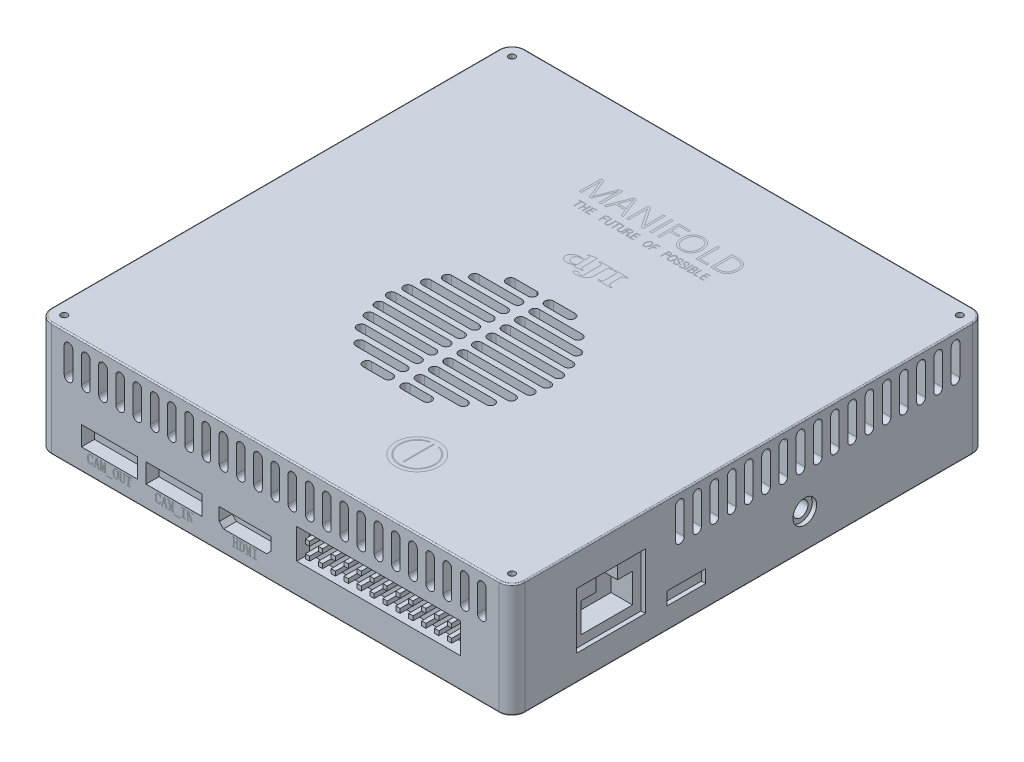
SolidWorks part; units mm, degrees
ref_plane "前视基准面" through (0, 0, 0) normal (0, 0, 1) x (1, 0, 0)
ref_plane "上视基准面" through (0, 0, 0) normal (0, 1, 0) x (1, 0, 0)
ref_plane "右视基准面" through (0, 0, 0) normal (1, 0, 0) x (0, 0, -1)
sketch "草图1" plane through (0, 0, 0) normal (0, 1, 0) x (1, 0, 0)
  line L1 (-55, -55) -> (55, -55)
  line L2 (-55, -55) -> (-55, 55)
  line L3 (-55, 55) -> (55, 55)
  line L4 (55, -55) -> (55, 55)
  line L5 (-55, -55) -> (55, 55) construction
  line L6 (-55, 55) -> (55, -55) construction
  point P0 (0, 0)
  dimension "D1" = 110
extrude "凸台-拉伸1" add sketch "草图1" along normal blind 26.5
fillet "圆角1" radius 3 4 edges at (-55, 13.25, -55) (-55, 13.25, 55) (55, 13.25, -55) (55, 13.25, 55)
sketch "草图2" plane through (0, 26.5, 0) normal (0, 1, 0) x (1, 0, 0)
  line L0 (-55, 33) -> (55, 33) construction
  line L1 (-55, 52) -> (-55, -52) construction
  line L2 (55, -52) -> (55, 52) construction
  line L3 (-55, 29) -> (55, 29) construction
  line L4 (-55, 17) -> (55, 17) construction
  line L5 (52, 55) -> (-52, 55) construction
  line L6 (-52, -55) -> (52, -55) construction
  circle A0 centre (17, -39) radius 5
  text T0 "MANIFOLD" font "@等线" height 5
  text T1 "THE FUTURE OF POSSIBLE" font "汉仪长仿宋体" height 2
  text T2 "dJI" font "@草檀斋毛泽东字体" height 4
  dimension "D4" = 16
  dimension "D5" = 38
  dimension "D6" = 10
  dimension "D1" = 22
  dimension "D2" = 26
  dimension "D3" = 38
split line "分割线1"
sketch "草图3" plane through (0, 26.5, 0) normal (0, 1, 0) x (1, 0, 0)
  line L0 (17, -35) -> (17, -42)
  line L1 (17, -35) -> (17, -34) construction
  line L2 (16.8, -35) -> (16.8, -42)
  arc A0 (15.9647, -35.1363) -> (18.0353, -35.1363) centre (17, -39) ccw
  circle A1 centre (17, -39) radius 5 construction
  arc A2 (15.913, -34.9431) -> (18.087, -34.9431) centre (17, -39) ccw
  arc A3 (18.0353, -35.1363) -> (18.087, -34.9431) centre (18.0612, -35.0397) cw
  arc A4 (15.9647, -35.1363) -> (15.913, -34.9431) centre (15.9388, -35.0397) ccw
  arc A5 (16.8, -35) -> (17, -35) centre (16.9, -35) cw
  arc A6 (16.8, -42) -> (17, -42) centre (16.9, -42) ccw
  dimension "D1" = 4
  dimension "D2" = 4
  dimension "D3" = 7
  dimension "D4" = 30
  dimension "D5" = 0.2
  dimension "D6" = 0.2
split line "分割线3"
sketch "草图4" plane through (0, 26.5, 0) normal (0, 1, 0) x (1, 0, 0)
  line L0 (-52, -55) -> (52, -55) construction
  line L1 (0, 10) -> (0, -30) construction
  line L2 (0, 6.6667) -> (2, 6.6667) construction
  line L3 (0, -26.6667) -> (2, -26.6667) construction
  line L4 (2, -26.6667) -> (2, 6.6667) construction
  line L5 (2, 6.6667) -> (7, 6.6667) construction
  line L6 (2, 7.6667) -> (7, 7.6667)
  line L7 (2, 5.6667) -> (7, 5.6667)
  line L8 (2, 3.3333) -> (12, 3.3333) construction
  line L9 (2, 4.3333) -> (12, 4.3333)
  line L10 (2, 2.3333) -> (12, 2.3333)
  line L11 (2, 0) -> (15, 0) construction
  line L12 (2, 1) -> (15, 1)
  line L13 (2, -1) -> (15, -1)
  line L14 (2, -3.3333) -> (16.5, -3.3333) construction
  line L15 (2, -2.3333) -> (16.5, -2.3333)
  line L16 (2, -4.3333) -> (16.5, -4.3333)
  line L17 (2, -6.6667) -> (17.5, -6.6667) construction
  line L18 (2, -5.6667) -> (17.5, -5.6667)
  line L19 (2, -7.6667) -> (17.5, -7.6667)
  line L20 (2, -10) -> (18, -10) construction
  line L21 (2, -9) -> (18, -9)
  line L22 (2, -11) -> (18, -11)
  line L23 (-20, -10) -> (20, -10) construction
  line L24 (2, -13.3333) -> (17.5, -13.3333) construction
  line L25 (2, -14.3333) -> (17.5, -14.3333)
  line L26 (2, -12.3333) -> (17.5, -12.3333)
  line L27 (2, -16.6667) -> (16.5, -16.6667) construction
  line L28 (2, -17.6667) -> (16.5, -17.6667)
  line L29 (2, -15.6667) -> (16.5, -15.6667)
  line L30 (2, -20) -> (15, -20) construction
  line L31 (2, -21) -> (15, -21)
  line L32 (2, -19) -> (15, -19)
  line L33 (2, -23.3333) -> (12, -23.3333) construction
  line L34 (2, -24.3333) -> (12, -24.3333)
  line L35 (2, -22.3333) -> (12, -22.3333)
  line L36 (2, -26.6667) -> (7, -26.6667) construction
  line L37 (2, -27.6667) -> (7, -27.6667)
  line L38 (2, -25.6667) -> (7, -25.6667)
  line L39 (-2, -26.6667) -> (-7, -26.6667) construction
  line L40 (-2, -27.6667) -> (-7, -27.6667)
  line L41 (-2, -25.6667) -> (-7, -25.6667)
  line L42 (-2, 6.6667) -> (-7, 6.6667) construction
  line L43 (-2, 7.6667) -> (-7, 7.6667)
  line L44 (-2, 5.6667) -> (-7, 5.6667)
  line L45 (-2, 3.3333) -> (-12, 3.3333) construction
  line L46 (-2, 4.3333) -> (-12, 4.3333)
  line L47 (-2, 2.3333) -> (-12, 2.3333)
  line L48 (-2, 0) -> (-15, 0) construction
  line L49 (-2, 1) -> (-15, 1)
  line L50 (-2, -1) -> (-15, -1)
  line L51 (-2, -23.3333) -> (-12, -23.3333) construction
  line L52 (-2, -24.3333) -> (-12, -24.3333)
  line L53 (-2, -22.3333) -> (-12, -22.3333)
  line L54 (-2, -20) -> (-15, -20) construction
  line L55 (-2, -21) -> (-15, -21)
  line L56 (-2, -19) -> (-15, -19)
  line L57 (-2, -16.6667) -> (-16.5, -16.6667) construction
  line L58 (-2, -17.6667) -> (-16.5, -17.6667)
  line L59 (-2, -15.6667) -> (-16.5, -15.6667)
  line L60 (-2, -13.3333) -> (-17.5, -13.3333) construction
  line L61 (-2, -14.3333) -> (-17.5, -14.3333)
  line L62 (-2, -12.3333) -> (-17.5, -12.3333)
  line L63 (-2, -10) -> (-18, -10) construction
  line L64 (-2, -9) -> (-18, -9)
  line L65 (-2, -11) -> (-18, -11)
  line L66 (-2, -6.6667) -> (-17.5, -6.6667) construction
  line L67 (-2, -5.6667) -> (-17.5, -5.6667)
  line L68 (-2, -7.6667) -> (-17.5, -7.6667)
  line L69 (-2, -3.3333) -> (-16.5, -3.3333) construction
  line L70 (-2, -2.3333) -> (-16.5, -2.3333)
  line L71 (-2, -4.3333) -> (-16.5, -4.3333)
  circle A0 centre (0, -10) radius 20 construction
  arc A1 (2, 7.6667) -> (2, 5.6667) centre (2, 6.6667) ccw
  arc A2 (7, 5.6667) -> (7, 7.6667) centre (7, 6.6667) ccw
  arc A3 (2, 4.3333) -> (2, 2.3333) centre (2, 3.3333) ccw
  arc A4 (12, 2.3333) -> (12, 4.3333) centre (12, 3.3333) ccw
  arc A5 (2, 1) -> (2, -1) centre (2, 0) ccw
  arc A6 (15, -1) -> (15, 1) centre (15, 0) ccw
  arc A7 (2, -2.3333) -> (2, -4.3333) centre (2, -3.3333) ccw
  arc A8 (16.5, -4.3333) -> (16.5, -2.3333) centre (16.5, -3.3333) ccw
  arc A9 (2, -5.6667) -> (2, -7.6667) centre (2, -6.6667) ccw
  arc A10 (17.5, -7.6667) -> (17.5, -5.6667) centre (17.5, -6.6667) ccw
  arc A11 (2, -9) -> (2, -11) centre (2, -10) ccw
  arc A12 (18, -11) -> (18, -9) centre (18, -10) ccw
  arc A13 (2, -14.3333) -> (2, -12.3333) centre (2, -13.3333) cw
  arc A14 (17.5, -12.3333) -> (17.5, -14.3333) centre (17.5, -13.3333) cw
  arc A15 (2, -17.6667) -> (2, -15.6667) centre (2, -16.6667) cw
  arc A16 (16.5, -15.6667) -> (16.5, -17.6667) centre (16.5, -16.6667) cw
  arc A17 (2, -21) -> (2, -19) centre (2, -20) cw
  arc A18 (15, -19) -> (15, -21) centre (15, -20) cw
  arc A19 (2, -24.3333) -> (2, -22.3333) centre (2, -23.3333) cw
  arc A20 (12, -22.3333) -> (12, -24.3333) centre (12, -23.3333) cw
  arc A21 (2, -27.6667) -> (2, -25.6667) centre (2, -26.6667) cw
  arc A22 (7, -25.6667) -> (7, -27.6667) centre (7, -26.6667) cw
  arc A23 (-2, -27.6667) -> (-2, -25.6667) centre (-2, -26.6667) ccw
  arc A24 (-7, -25.6667) -> (-7, -27.6667) centre (-7, -26.6667) ccw
  arc A25 (-2, 7.6667) -> (-2, 5.6667) centre (-2, 6.6667) cw
  arc A26 (-7, 5.6667) -> (-7, 7.6667) centre (-7, 6.6667) cw
  arc A27 (-2, 4.3333) -> (-2, 2.3333) centre (-2, 3.3333) cw
  arc A28 (-12, 2.3333) -> (-12, 4.3333) centre (-12, 3.3333) cw
  arc A29 (-2, 1) -> (-2, -1) centre (-2, 0) cw
  arc A30 (-15, -1) -> (-15, 1) centre (-15, 0) cw
  arc A31 (-2, -24.3333) -> (-2, -22.3333) centre (-2, -23.3333) ccw
  arc A32 (-12, -22.3333) -> (-12, -24.3333) centre (-12, -23.3333) ccw
  arc A33 (-2, -21) -> (-2, -19) centre (-2, -20) ccw
  arc A34 (-15, -19) -> (-15, -21) centre (-15, -20) ccw
  arc A35 (-2, -17.6667) -> (-2, -15.6667) centre (-2, -16.6667) ccw
  arc A36 (-16.5, -15.6667) -> (-16.5, -17.6667) centre (-16.5, -16.6667) ccw
  arc A37 (-2, -14.3333) -> (-2, -12.3333) centre (-2, -13.3333) ccw
  arc A38 (-17.5, -12.3333) -> (-17.5, -14.3333) centre (-17.5, -13.3333) ccw
  arc A39 (-2, -9) -> (-2, -11) centre (-2, -10) cw
  arc A40 (-18, -11) -> (-18, -9) centre (-18, -10) cw
  arc A41 (-2, -5.6667) -> (-2, -7.6667) centre (-2, -6.6667) cw
  arc A42 (-17.5, -7.6667) -> (-17.5, -5.6667) centre (-17.5, -6.6667) cw
  arc A43 (-2, -2.3333) -> (-2, -4.3333) centre (-2, -3.3333) cw
  arc A44 (-16.5, -4.3333) -> (-16.5, -2.3333) centre (-16.5, -3.3333) cw
  point P5 (0, -55)
  point P11 (2, -23.3333)
  point P12 (2, -20)
  point P13 (2, -16.6667)
  point P14 (2, -13.3333)
  point P15 (2, -10)
  point P16 (2, -6.6667)
  point P17 (2, -3.3333)
  point P18 (2, 0)
  point P19 (2, 3.3333)
  point P20 (4.5, 6.6667)
  point P26 (7, 3.3333)
  point P33 (8.5, 0)
  point P42 (9.25, -3.3333)
  point P47 (9.75, -6.6667)
  point P49 (0, 6.6667)
  point P50 (0, 3.3333)
  point P51 (0, 0)
  point P52 (0, -3.3333)
  point P53 (0, -6.6667)
  point P54 (0, -10)
  point P55 (0, -13.3333)
  point P56 (0, -16.6667)
  point P57 (0, -20)
  point P58 (0, -23.3333)
  point P59 (0, -26.6667)
  point P66 (10, -10)
  point P76 (9.75, -13.3333)
  point P83 (9.25, -16.6667)
  point P90 (8.5, -20)
  point P97 (7, -23.3333)
  point P103 (4.5, -26.6667)
  point P110 (-4.5, -26.6667)
  point P117 (-4.5, 6.6667)
  point P124 (-7, 3.3333)
  point P131 (-8.5, 0)
  point P139 (-7, -23.3333)
  point P146 (-8.5, -20)
  point P153 (-9.25, -16.6667)
  point P160 (-9.75, -13.3333)
  point P167 (-10, -10)
  point P174 (-9.75, -6.6667)
  point P181 (-9.25, -3.3333)
  dimension "D1" = 40
  dimension "D3" = 1
  dimension "D4" = 1
  dimension "D5" = 1
  dimension "D6" = 1
  dimension "D7" = 1
  dimension "D8" = 1
  dimension "D9" = 2
  dimension "D2" = 45
  dimension "D10" = 5
  dimension "D11" = 10
  dimension "D12" = 13
  dimension "D13" = 14.5
  dimension "D14" = 15.5
  dimension "D15" = 16
extrude "切除-拉伸1" cut sketch "草图4" against normal blind 6
sketch "草图5" plane through (0, 0, 55) normal (0, 0, 1) x (1, 0, 0)
  line L0 (55, 26.5) -> (55, 0) construction
  line L1 (5, 14) -> (43, 14)
  line L2 (5, 14) -> (5, 7)
  line L3 (5, 7) -> (43, 7)
  line L4 (43, 14) -> (43, 7)
  line L5 (-52, 0) -> (52, 0) construction
  line L6 (-13, 9) -> (-1, 9)
  line L7 (-1, 9) -> (-1, 6)
  line L8 (-1, 6) -> (-2, 5)
  line L9 (-2, 5) -> (-12, 5)
  line L10 (-12, 5) -> (-13, 6)
  line L11 (-13, 6) -> (-13, 9)
  line L12 (-55, 0) -> (-55, 26.5) construction
  line L13 (-45, 9.5) -> (-32, 9.5)
  line L14 (-45, 9.5) -> (-45, 5)
  line L15 (-45, 5) -> (-32, 5)
  line L16 (-32, 9.5) -> (-32, 5)
  line L17 (-30, 9.5) -> (-17, 9.5)
  line L18 (-30, 9.5) -> (-30, 5)
  line L19 (-30, 5) -> (-17, 5)
  line L20 (-17, 9.5) -> (-17, 5)
  line L21 (10, 12.5) -> (11, 12.5)
  line L22 (7, 12.5) -> (8, 12.5)
  line L23 (7, 12.5) -> (7, 11.5)
  line L24 (7, 11.5) -> (8, 11.5)
  line L25 (8, 12.5) -> (8, 11.5)
  line L26 (11, 12.5) -> (11, 11.5)
  line L27 (10, 11.5) -> (11, 11.5)
  line L28 (10, 12.5) -> (10, 11.5)
  line L29 (13, 12.5) -> (14, 12.5)
  line L30 (14, 12.5) -> (14, 11.5)
  line L31 (13, 11.5) -> (14, 11.5)
  line L32 (13, 12.5) -> (13, 11.5)
  line L33 (16, 12.5) -> (17, 12.5)
  line L34 (17, 12.5) -> (17, 11.5)
  line L35 (16, 11.5) -> (17, 11.5)
  line L36 (16, 12.5) -> (16, 11.5)
  line L37 (19, 12.5) -> (20, 12.5)
  line L38 (20, 12.5) -> (20, 11.5)
  line L39 (19, 11.5) -> (20, 11.5)
  line L40 (19, 12.5) -> (19, 11.5)
  line L41 (22, 12.5) -> (23, 12.5)
  line L42 (23, 12.5) -> (23, 11.5)
  line L43 (22, 11.5) -> (23, 11.5)
  line L44 (22, 12.5) -> (22, 11.5)
  line L45 (25, 12.5) -> (26, 12.5)
  line L46 (26, 12.5) -> (26, 11.5)
  line L47 (25, 11.5) -> (26, 11.5)
  line L48 (25, 12.5) -> (25, 11.5)
  line L49 (28, 12.5) -> (29, 12.5)
  line L50 (29, 12.5) -> (29, 11.5)
  line L51 (28, 11.5) -> (29, 11.5)
  line L52 (28, 12.5) -> (28, 11.5)
  line L53 (31, 12.5) -> (32, 12.5)
  line L54 (32, 12.5) -> (32, 11.5)
  line L55 (31, 11.5) -> (32, 11.5)
  line L56 (31, 12.5) -> (31, 11.5)
  line L57 (34, 12.5) -> (35, 12.5)
  line L58 (35, 12.5) -> (35, 11.5)
  line L59 (34, 11.5) -> (35, 11.5)
  line L60 (34, 12.5) -> (34, 11.5)
  line L61 (37, 12.5) -> (38, 12.5)
  line L62 (38, 12.5) -> (38, 11.5)
  line L63 (37, 11.5) -> (38, 11.5)
  line L64 (37, 12.5) -> (37, 11.5)
  line L65 (40, 12.5) -> (41, 12.5)
  line L66 (41, 12.5) -> (41, 11.5)
  line L67 (40, 11.5) -> (41, 11.5)
  line L68 (40, 12.5) -> (40, 11.5)
  line L69 (10, 9.5) -> (11, 9.5)
  line L70 (11, 9.5) -> (11, 8.5)
  line L71 (10, 8.5) -> (11, 8.5)
  line L72 (10, 9.5) -> (10, 8.5)
  line L73 (13, 9.5) -> (14, 9.5)
  line L74 (14, 9.5) -> (14, 8.5)
  line L75 (13, 8.5) -> (14, 8.5)
  line L76 (13, 9.5) -> (13, 8.5)
  line L77 (16, 9.5) -> (17, 9.5)
  line L78 (17, 9.5) -> (17, 8.5)
  line L79 (16, 8.5) -> (17, 8.5)
  line L80 (16, 9.5) -> (16, 8.5)
  line L81 (19, 9.5) -> (20, 9.5)
  line L82 (20, 9.5) -> (20, 8.5)
  line L83 (19, 8.5) -> (20, 8.5)
  line L84 (19, 9.5) -> (19, 8.5)
  line L85 (22, 9.5) -> (23, 9.5)
  line L86 (23, 9.5) -> (23, 8.5)
  line L87 (22, 8.5) -> (23, 8.5)
  line L88 (22, 9.5) -> (22, 8.5)
  line L89 (25, 9.5) -> (26, 9.5)
  line L90 (26, 9.5) -> (26, 8.5)
  line L91 (25, 8.5) -> (26, 8.5)
  line L92 (25, 9.5) -> (25, 8.5)
  line L93 (28, 9.5) -> (29, 9.5)
  line L94 (29, 9.5) -> (29, 8.5)
  line L95 (28, 8.5) -> (29, 8.5)
  line L96 (28, 9.5) -> (28, 8.5)
  line L97 (31, 9.5) -> (32, 9.5)
  line L98 (32, 9.5) -> (32, 8.5)
  line L99 (31, 8.5) -> (32, 8.5)
  line L100 (31, 9.5) -> (31, 8.5)
  line L101 (34, 9.5) -> (35, 9.5)
  line L102 (35, 9.5) -> (35, 8.5)
  line L103 (34, 8.5) -> (35, 8.5)
  line L104 (34, 9.5) -> (34, 8.5)
  line L105 (37, 9.5) -> (38, 9.5)
  line L106 (38, 9.5) -> (38, 8.5)
  line L107 (37, 8.5) -> (38, 8.5)
  line L108 (37, 9.5) -> (37, 8.5)
  line L109 (40, 9.5) -> (41, 9.5)
  line L110 (41, 9.5) -> (41, 8.5)
  line L111 (40, 8.5) -> (41, 8.5)
  line L112 (40, 9.5) -> (40, 8.5)
  line L113 (7, 9.5) -> (8, 9.5)
  line L114 (8, 9.5) -> (8, 8.5)
  line L115 (7, 8.5) -> (8, 8.5)
  line L116 (7, 9.5) -> (7, 8.5)
  line L117 (7, 12.5) -> (10, 12.5) construction
  line L118 (7, 12.5) -> (7, 9.5) construction
  point P16 (-7, 5)
  point P17 (-7, 9)
  point P25 (-30, 7.25)
  dimension "D1" = 12
  dimension "D2" = 7
  dimension "D3" = 38
  dimension "D4" = 7
  dimension "D5" = 12
  dimension "D6" = 4
  dimension "D7" = 3
  dimension "D8" = 10
  dimension "D9" = 5
  dimension "D10" = 6
  dimension "D11" = 4.5
  dimension "D12" = 5
  dimension "D13" = 13
  dimension "D14" = 2
  dimension "D15" = 10
  dimension "D16" = 1
  dimension "D17" = 1.5
  dimension "D18" = 2
  dimension "D21" = 3
  dimension "D22" = 3
  dimension "D19" = 12
  dimension "D20" = 2
extrude "切除-拉伸2" cut sketch "草图5" against normal blind 3
sketch "草图6" plane through (55, 0, 0) normal (1, 0, 0) x (0, 0, -1)
  line L0 (-52, 0) -> (52, 0) construction
  line L1 (-40, 6) -> (-24, 6)
  line L2 (-40, 6) -> (-40, 19)
  line L3 (-40, 19) -> (-24, 19)
  line L4 (-24, 6) -> (-24, 19)
  line L5 (-55, 0) -> (-55, 26.5) construction
  line L6 (55, 26.5) -> (55, 0) construction
  line L7 (-19, 8) -> (-10, 8)
  line L8 (-19, 8) -> (-19, 5)
  line L9 (-19, 5) -> (-10, 5)
  line L10 (-10, 8) -> (-10, 5)
  circle A0 centre (13, 8) radius 2.75
  dimension "D9" = 5.5
  dimension "D10" = 8
  dimension "D11" = 42
  dimension "D1" = 6
  dimension "D2" = 16
  dimension "D3" = 13
  dimension "D4" = 15
  dimension "D5" = 5
  dimension "D6" = 3
  dimension "D7" = 9
  dimension "D8" = 5
extrude "切除-拉伸3" cut sketch "草图6" against normal blind 1
sketch "草图7" plane through (54, 0, 0) normal (1, 0, 0) x (0, 0, -1)
  line L0 (-29.5, 15) -> (-26, 15)
  line L1 (-38, 8.2) -> (-26, 8.2)
  line L2 (-38, 8.2) -> (-38, 15)
  line L3 (-38, 15) -> (-34.5, 15)
  line L4 (-26, 8.2) -> (-26, 15)
  line L5 (-34.5, 18.5) -> (-29.5, 18.5)
  line L6 (-34.5, 18.5) -> (-34.5, 15)
  line L7 (-40, 6) -> (-24, 6) construction
  line L8 (-29.5, 18.5) -> (-29.5, 15)
  line L9 (-24, 6) -> (-24, 19) construction
  line L10 (-40, 6) -> (-24, 6) construction
  line L11 (-24, 19) -> (-40, 19) construction
  point P13 (-32, 8.2)
  point P16 (-32, 6)
  dimension "D1" = 2.2
  dimension "D2" = 2
  dimension "D3" = 5
  dimension "D4" = 4
  dimension "D5" = 0.5
extrude "切除-拉伸4" cut sketch "草图7" against normal blind 5
sketch "草图8" plane through (-55, 0, 0) normal (-1, 0, 0) x (0, 0, 1)
  line L0 (-52, 0) -> (52, 0) construction
  line L1 (38, 19) -> (44, 19)
  line L2 (38, 19) -> (38, 6)
  line L3 (38, 6) -> (44, 6)
  line L4 (44, 19) -> (44, 6)
  line L5 (28.5, 19) -> (34.5, 19)
  line L6 (28.5, 19) -> (28.5, 6)
  line L7 (28.5, 6) -> (34.5, 6)
  line L8 (34.5, 19) -> (34.5, 6)
  line L9 (10, 21) -> (25, 21)
  line L10 (10, 21) -> (10, 6)
  line L11 (10, 6) -> (25, 6)
  line L12 (25, 21) -> (25, 6)
  line L13 (-13.5, 9.5) -> (-5.5, 9.5)
  line L14 (-13.5, 9.5) -> (-13.5, 5)
  line L15 (-13.5, 5) -> (-5.5, 5)
  line L16 (-5.5, 9.5) -> (-5.5, 5)
  line L17 (-4, 9.5) -> (6.5, 9.5)
  line L18 (-4, 9.5) -> (-4, 5)
  line L19 (-4, 5) -> (6.5, 5)
  line L20 (6.5, 9.5) -> (6.5, 5)
  line L21 (-44, 17) -> (-31, 17)
  line L22 (-44, 17) -> (-44, 6)
  line L23 (-44, 6) -> (-31, 6)
  line L24 (-31, 17) -> (-31, 6)
  line L25 (55, 26.5) -> (55, 0) construction
  line L26 (-55, 0) -> (-55, 26.5) construction
  point P24 (31.5, 19)
  point P30 (28.5, 12.5)
  dimension "D1" = 6
  dimension "D2" = 13
  dimension "D3" = 6
  dimension "D4" = 11
  dimension "D5" = 3.5
  dimension "D6" = 3.5
  dimension "D7" = 6
  dimension "D8" = 15
  dimension "D9" = 5
  dimension "D10" = 4.5
  dimension "D11" = 10.5
  dimension "D12" = 8
  dimension "D13" = 1.5
  dimension "D14" = 3.5
  dimension "D15" = 11
  dimension "D16" = 11
  dimension "D17" = 13
  dimension "D18" = 6
extrude "切除-拉伸5" cut sketch "草图8" against normal blind 1
sketch "草图9" plane through (55, 0, 0) normal (1, 0, 0) x (0, 0, -1)
  line L0 (-52, 26.5) -> (52, 26.5) construction
  line L1 (48, 24) -> (48, 17) construction
  line L2 (49, 24) -> (49, 17)
  line L3 (-16, 14.5) -> (52, 14.5) construction
  line L4 (47, 24) -> (47, 17)
  line L5 (52, 0) -> (52, 26.5) construction
  line L6 (44, 24) -> (44, 17) construction
  line L7 (45, 24) -> (45, 17)
  line L8 (43, 24) -> (43, 17)
  line L9 (40, 24) -> (40, 17) construction
  line L10 (41, 24) -> (41, 17)
  line L11 (39, 24) -> (39, 17)
  line L12 (36, 24) -> (36, 17) construction
  line L13 (37, 24) -> (37, 17)
  line L14 (35, 24) -> (35, 17)
  line L15 (32, 24) -> (32, 17) construction
  line L16 (33, 24) -> (33, 17)
  line L17 (31, 24) -> (31, 17)
  line L18 (28, 24) -> (28, 17) construction
  line L19 (29, 24) -> (29, 17)
  line L20 (27, 24) -> (27, 17)
  line L21 (24, 24) -> (24, 17) construction
  line L22 (25, 24) -> (25, 17)
  line L23 (23, 24) -> (23, 17)
  line L24 (20, 24) -> (20, 17) construction
  line L25 (21, 24) -> (21, 17)
  line L26 (19, 24) -> (19, 17)
  line L27 (16, 24) -> (16, 17) construction
  line L28 (17, 24) -> (17, 17)
  line L29 (15, 24) -> (15, 17)
  line L30 (12, 24) -> (12, 17) construction
  line L31 (13, 24) -> (13, 17)
  line L32 (11, 24) -> (11, 17)
  line L33 (8, 24) -> (8, 17) construction
  line L34 (9, 24) -> (9, 17)
  line L35 (7, 24) -> (7, 17)
  line L36 (4, 24) -> (4, 17) construction
  line L37 (5, 24) -> (5, 17)
  line L38 (3, 24) -> (3, 17)
  line L39 (0, 24) -> (0, 17) construction
  line L40 (1, 24) -> (1, 17)
  line L41 (-1, 24) -> (-1, 17)
  line L42 (-4, 24) -> (-4, 17) construction
  line L43 (-3, 24) -> (-3, 17)
  line L44 (-5, 24) -> (-5, 17)
  line L45 (-8, 24) -> (-8, 17) construction
  line L46 (-7, 24) -> (-7, 17)
  line L47 (-9, 24) -> (-9, 17)
  line L48 (-12, 24) -> (-12, 17) construction
  line L49 (-11, 24) -> (-11, 17)
  line L50 (-13, 24) -> (-13, 17)
  line L51 (-16, 24) -> (-16, 17) construction
  line L52 (-15, 24) -> (-15, 17)
  line L53 (-17, 24) -> (-17, 17)
  arc A0 (49, 24) -> (47, 24) centre (48, 24) ccw
  arc A1 (47, 17) -> (49, 17) centre (48, 17) ccw
  arc A2 (45, 24) -> (43, 24) centre (44, 24) ccw
  arc A3 (43, 17) -> (45, 17) centre (44, 17) ccw
  arc A4 (41, 24) -> (39, 24) centre (40, 24) ccw
  arc A5 (39, 17) -> (41, 17) centre (40, 17) ccw
  arc A6 (37, 24) -> (35, 24) centre (36, 24) ccw
  arc A7 (35, 17) -> (37, 17) centre (36, 17) ccw
  arc A8 (33, 24) -> (31, 24) centre (32, 24) ccw
  arc A9 (31, 17) -> (33, 17) centre (32, 17) ccw
  arc A10 (29, 24) -> (27, 24) centre (28, 24) ccw
  arc A11 (27, 17) -> (29, 17) centre (28, 17) ccw
  arc A12 (25, 24) -> (23, 24) centre (24, 24) ccw
  arc A13 (23, 17) -> (25, 17) centre (24, 17) ccw
  arc A14 (21, 24) -> (19, 24) centre (20, 24) ccw
  arc A15 (19, 17) -> (21, 17) centre (20, 17) ccw
  arc A16 (17, 24) -> (15, 24) centre (16, 24) ccw
  arc A17 (15, 17) -> (17, 17) centre (16, 17) ccw
  arc A18 (13, 24) -> (11, 24) centre (12, 24) ccw
  arc A19 (11, 17) -> (13, 17) centre (12, 17) ccw
  arc A20 (9, 24) -> (7, 24) centre (8, 24) ccw
  arc A21 (7, 17) -> (9, 17) centre (8, 17) ccw
  arc A22 (5, 24) -> (3, 24) centre (4, 24) ccw
  arc A23 (3, 17) -> (5, 17) centre (4, 17) ccw
  arc A24 (1, 24) -> (-1, 24) centre (0, 24) ccw
  arc A25 (-1, 17) -> (1, 17) centre (0, 17) ccw
  arc A26 (-3, 24) -> (-5, 24) centre (-4, 24) ccw
  arc A27 (-5, 17) -> (-3, 17) centre (-4, 17) ccw
  arc A28 (-7, 24) -> (-9, 24) centre (-8, 24) ccw
  arc A29 (-9, 17) -> (-7, 17) centre (-8, 17) ccw
  arc A30 (-11, 24) -> (-13, 24) centre (-12, 24) ccw
  arc A31 (-13, 17) -> (-11, 17) centre (-12, 17) ccw
  arc A32 (-15, 24) -> (-17, 24) centre (-16, 24) ccw
  arc A33 (-17, 17) -> (-15, 17) centre (-16, 17) ccw
  point P6 (48, 20.5)
  point P16 (44, 20.5)
  point P23 (40, 20.5)
  point P30 (36, 20.5)
  point P37 (32, 20.5)
  point P44 (28, 20.5)
  point P51 (24, 20.5)
  point P58 (20, 20.5)
  point P65 (16, 20.5)
  point P72 (12, 20.5)
  point P79 (8, 20.5)
  point P86 (4, 20.5)
  point P93 (0, 20.5)
  point P100 (-4, 20.5)
  point P107 (-8, 20.5)
  point P114 (-12, 20.5)
  point P121 (-16, 20.5)
  dimension "D2" = 1
  dimension "D1" = 12
  dimension "D3" = 4
  dimension "D4" = 7
  dimension "D5" = 2.5
  dimension "D7" = 4
  dimension "D6" = 17
extrude "切除-拉伸6" cut sketch "草图9" against normal blind 5
sketch "草图10" plane through (0, 0, -55) normal (0, 0, -1) x (-1, 0, 0)
  line L0 (-48, 24) -> (-48, 17) construction
  line L1 (-47, 24) -> (-47, 17)
  line L2 (-49, 24) -> (-49, 17)
  line L3 (-52, 26.5) -> (52, 26.5) construction
  line L4 (-52, 26.5) -> (-52, 0) construction
  line L5 (-44, 24) -> (-44, 17) construction
  line L6 (-43, 24) -> (-43, 17)
  line L7 (-45, 24) -> (-45, 17)
  line L8 (-40, 24) -> (-40, 17) construction
  line L9 (-39, 24) -> (-39, 17)
  line L10 (-41, 24) -> (-41, 17)
  line L11 (-36, 24) -> (-36, 17) construction
  line L12 (-35, 24) -> (-35, 17)
  line L13 (-37, 24) -> (-37, 17)
  line L14 (-32, 24) -> (-32, 17) construction
  line L15 (-31, 24) -> (-31, 17)
  line L16 (-33, 24) -> (-33, 17)
  line L17 (-28, 24) -> (-28, 17) construction
  line L18 (-27, 24) -> (-27, 17)
  line L19 (-29, 24) -> (-29, 17)
  line L20 (-24, 24) -> (-24, 17) construction
  line L21 (-23, 24) -> (-23, 17)
  line L22 (-25, 24) -> (-25, 17)
  line L23 (-20, 24) -> (-20, 17) construction
  line L24 (-19, 24) -> (-19, 17)
  line L25 (-21, 24) -> (-21, 17)
  line L26 (-16, 24) -> (-16, 17) construction
  line L27 (-15, 24) -> (-15, 17)
  line L28 (-17, 24) -> (-17, 17)
  line L29 (-12, 24) -> (-12, 17) construction
  line L30 (-11, 24) -> (-11, 17)
  line L31 (-13, 24) -> (-13, 17)
  line L32 (-8, 24) -> (-8, 17) construction
  line L33 (-7, 24) -> (-7, 17)
  line L34 (-9, 24) -> (-9, 17)
  line L35 (-4, 24) -> (-4, 17) construction
  line L36 (-3, 24) -> (-3, 17)
  line L37 (-5, 24) -> (-5, 17)
  line L38 (0, 24) -> (0, 17) construction
  line L39 (1, 24) -> (1, 17)
  line L40 (-1, 24) -> (-1, 17)
  line L41 (4, 24) -> (4, 17) construction
  line L42 (5, 24) -> (5, 17)
  line L43 (3, 24) -> (3, 17)
  line L44 (8, 24) -> (8, 17) construction
  line L45 (9, 24) -> (9, 17)
  line L46 (7, 24) -> (7, 17)
  line L47 (12, 24) -> (12, 17) construction
  line L48 (13, 24) -> (13, 17)
  line L49 (11, 24) -> (11, 17)
  line L50 (16, 24) -> (16, 17) construction
  line L51 (17, 24) -> (17, 17)
  line L52 (15, 24) -> (15, 17)
  line L53 (20, 24) -> (20, 17) construction
  line L54 (21, 24) -> (21, 17)
  line L55 (19, 24) -> (19, 17)
  line L56 (24, 24) -> (24, 17) construction
  line L57 (25, 24) -> (25, 17)
  line L58 (23, 24) -> (23, 17)
  line L59 (28, 24) -> (28, 17) construction
  line L60 (29, 24) -> (29, 17)
  line L61 (27, 24) -> (27, 17)
  line L62 (32, 24) -> (32, 17) construction
  line L63 (33, 24) -> (33, 17)
  line L64 (31, 24) -> (31, 17)
  line L65 (36, 24) -> (36, 17) construction
  line L66 (37, 24) -> (37, 17)
  line L67 (35, 24) -> (35, 17)
  line L68 (40, 24) -> (40, 17) construction
  line L69 (41, 24) -> (41, 17)
  line L70 (39, 24) -> (39, 17)
  line L71 (44, 24) -> (44, 17) construction
  line L72 (45, 24) -> (45, 17)
  line L73 (43, 24) -> (43, 17)
  line L74 (48, 24) -> (48, 17) construction
  line L75 (49, 24) -> (49, 17)
  line L76 (47, 24) -> (47, 17)
  line L77 (-48, 24) -> (-44, 24) construction
  arc A0 (-47, 24) -> (-49, 24) centre (-48, 24) ccw
  arc A1 (-49, 17) -> (-47, 17) centre (-48, 17) ccw
  arc A2 (-43, 24) -> (-45, 24) centre (-44, 24) ccw
  arc A3 (-45, 17) -> (-43, 17) centre (-44, 17) ccw
  arc A4 (-39, 24) -> (-41, 24) centre (-40, 24) ccw
  arc A5 (-41, 17) -> (-39, 17) centre (-40, 17) ccw
  arc A6 (-35, 24) -> (-37, 24) centre (-36, 24) ccw
  arc A7 (-37, 17) -> (-35, 17) centre (-36, 17) ccw
  arc A8 (-31, 24) -> (-33, 24) centre (-32, 24) ccw
  arc A9 (-33, 17) -> (-31, 17) centre (-32, 17) ccw
  arc A10 (-27, 24) -> (-29, 24) centre (-28, 24) ccw
  arc A11 (-29, 17) -> (-27, 17) centre (-28, 17) ccw
  arc A12 (-23, 24) -> (-25, 24) centre (-24, 24) ccw
  arc A13 (-25, 17) -> (-23, 17) centre (-24, 17) ccw
  arc A14 (-19, 24) -> (-21, 24) centre (-20, 24) ccw
  arc A15 (-21, 17) -> (-19, 17) centre (-20, 17) ccw
  arc A16 (-15, 24) -> (-17, 24) centre (-16, 24) ccw
  arc A17 (-17, 17) -> (-15, 17) centre (-16, 17) ccw
  arc A18 (-11, 24) -> (-13, 24) centre (-12, 24) ccw
  arc A19 (-13, 17) -> (-11, 17) centre (-12, 17) ccw
  arc A20 (-7, 24) -> (-9, 24) centre (-8, 24) ccw
  arc A21 (-9, 17) -> (-7, 17) centre (-8, 17) ccw
  arc A22 (-3, 24) -> (-5, 24) centre (-4, 24) ccw
  arc A23 (-5, 17) -> (-3, 17) centre (-4, 17) ccw
  arc A24 (1, 24) -> (-1, 24) centre (0, 24) ccw
  arc A25 (-1, 17) -> (1, 17) centre (0, 17) ccw
  arc A26 (5, 24) -> (3, 24) centre (4, 24) ccw
  arc A27 (3, 17) -> (5, 17) centre (4, 17) ccw
  arc A28 (9, 24) -> (7, 24) centre (8, 24) ccw
  arc A29 (7, 17) -> (9, 17) centre (8, 17) ccw
  arc A30 (13, 24) -> (11, 24) centre (12, 24) ccw
  arc A31 (11, 17) -> (13, 17) centre (12, 17) ccw
  arc A32 (17, 24) -> (15, 24) centre (16, 24) ccw
  arc A33 (15, 17) -> (17, 17) centre (16, 17) ccw
  arc A34 (21, 24) -> (19, 24) centre (20, 24) ccw
  arc A35 (19, 17) -> (21, 17) centre (20, 17) ccw
  arc A36 (25, 24) -> (23, 24) centre (24, 24) ccw
  arc A37 (23, 17) -> (25, 17) centre (24, 17) ccw
  arc A38 (29, 24) -> (27, 24) centre (28, 24) ccw
  arc A39 (27, 17) -> (29, 17) centre (28, 17) ccw
  arc A40 (33, 24) -> (31, 24) centre (32, 24) ccw
  arc A41 (31, 17) -> (33, 17) centre (32, 17) ccw
  arc A42 (37, 24) -> (35, 24) centre (36, 24) ccw
  arc A43 (35, 17) -> (37, 17) centre (36, 17) ccw
  arc A44 (41, 24) -> (39, 24) centre (40, 24) ccw
  arc A45 (39, 17) -> (41, 17) centre (40, 17) ccw
  arc A46 (45, 24) -> (43, 24) centre (44, 24) ccw
  arc A47 (43, 17) -> (45, 17) centre (44, 17) ccw
  arc A48 (49, 24) -> (47, 24) centre (48, 24) ccw
  arc A49 (47, 17) -> (49, 17) centre (48, 17) ccw
  point P2 (-48, 20.5)
  point P14 (-44, 20.5)
  point P21 (-40, 20.5)
  point P28 (-36, 20.5)
  point P35 (-32, 20.5)
  point P42 (-28, 20.5)
  point P49 (-24, 20.5)
  point P56 (-20, 20.5)
  point P63 (-16, 20.5)
  point P70 (-12, 20.5)
  point P77 (-8, 20.5)
  point P84 (-4, 20.5)
  point P91 (0, 20.5)
  point P98 (4, 20.5)
  point P105 (8, 20.5)
  point P112 (12, 20.5)
  point P119 (16, 20.5)
  point P126 (20, 20.5)
  point P133 (24, 20.5)
  point P140 (28, 20.5)
  point P147 (32, 20.5)
  point P154 (36, 20.5)
  point P161 (40, 20.5)
  point P168 (44, 20.5)
  point P175 (48, 20.5)
  dimension "D1" = 2.5
  dimension "D2" = 1
  dimension "D3" = 7
  dimension "D4" = 4
  dimension "D6" = 4
  dimension "D5" = 25
extrude "切除-拉伸7" cut sketch "草图10" against normal blind 5
sketch "草图11" plane through (0, 0, 55) normal (0, 0, 1) x (1, 0, 0)
  line L0 (-52, 26.5) -> (52, 26.5) construction
  line L1 (-52, 26.5) -> (-52, 0) construction
  line L2 (52, 0) -> (52, 26.5) construction
  line L3 (-52, 14.5) -> (52, 14.5) construction
  line L4 (-48, 17.5) -> (-48, 23.5) construction
  line L5 (-49, 17.5) -> (-49, 23.5)
  line L6 (-47, 17.5) -> (-47, 23.5)
  line L7 (-44, 17.5) -> (-44, 23.5) construction
  line L8 (-45, 17.5) -> (-45, 23.5)
  line L9 (-43, 17.5) -> (-43, 23.5)
  line L10 (-40, 17.5) -> (-40, 23.5) construction
  line L11 (-41, 17.5) -> (-41, 23.5)
  line L12 (-39, 17.5) -> (-39, 23.5)
  line L13 (-36, 17.5) -> (-36, 23.5) construction
  line L14 (-37, 17.5) -> (-37, 23.5)
  line L15 (-35, 17.5) -> (-35, 23.5)
  line L16 (-32, 17.5) -> (-32, 23.5) construction
  line L17 (-33, 17.5) -> (-33, 23.5)
  line L18 (-31, 17.5) -> (-31, 23.5)
  line L19 (-28, 17.5) -> (-28, 23.5) construction
  line L20 (-29, 17.5) -> (-29, 23.5)
  line L21 (-27, 17.5) -> (-27, 23.5)
  line L22 (-24, 17.5) -> (-24, 23.5) construction
  line L23 (-25, 17.5) -> (-25, 23.5)
  line L24 (-23, 17.5) -> (-23, 23.5)
  line L25 (-20, 17.5) -> (-20, 23.5) construction
  line L26 (-21, 17.5) -> (-21, 23.5)
  line L27 (-19, 17.5) -> (-19, 23.5)
  line L28 (-16, 17.5) -> (-16, 23.5) construction
  line L29 (-17, 17.5) -> (-17, 23.5)
  line L30 (-15, 17.5) -> (-15, 23.5)
  line L31 (-12, 17.5) -> (-12, 23.5) construction
  line L32 (-13, 17.5) -> (-13, 23.5)
  line L33 (-11, 17.5) -> (-11, 23.5)
  line L34 (-8, 17.5) -> (-8, 23.5) construction
  line L35 (-9, 17.5) -> (-9, 23.5)
  line L36 (-7, 17.5) -> (-7, 23.5)
  line L37 (-4, 17.5) -> (-4, 23.5) construction
  line L38 (-5, 17.5) -> (-5, 23.5)
  line L39 (-3, 17.5) -> (-3, 23.5)
  line L40 (0, 17.5) -> (0, 23.5) construction
  line L41 (-1, 17.5) -> (-1, 23.5)
  line L42 (1, 17.5) -> (1, 23.5)
  line L43 (4, 17.5) -> (4, 23.5) construction
  line L44 (3, 17.5) -> (3, 23.5)
  line L45 (5, 17.5) -> (5, 23.5)
  line L46 (8, 17.5) -> (8, 23.5) construction
  line L47 (7, 17.5) -> (7, 23.5)
  line L48 (9, 17.5) -> (9, 23.5)
  line L49 (12, 17.5) -> (12, 23.5) construction
  line L50 (11, 17.5) -> (11, 23.5)
  line L51 (13, 17.5) -> (13, 23.5)
  line L52 (16, 17.5) -> (16, 23.5) construction
  line L53 (15, 17.5) -> (15, 23.5)
  line L54 (17, 17.5) -> (17, 23.5)
  line L55 (20, 17.5) -> (20, 23.5) construction
  line L56 (19, 17.5) -> (19, 23.5)
  line L57 (21, 17.5) -> (21, 23.5)
  line L58 (24, 17.5) -> (24, 23.5) construction
  line L59 (23, 17.5) -> (23, 23.5)
  line L60 (25, 17.5) -> (25, 23.5)
  line L61 (28, 17.5) -> (28, 23.5) construction
  line L62 (27, 17.5) -> (27, 23.5)
  line L63 (29, 17.5) -> (29, 23.5)
  line L64 (32, 17.5) -> (32, 23.5) construction
  line L65 (31, 17.5) -> (31, 23.5)
  line L66 (33, 17.5) -> (33, 23.5)
  line L67 (36, 17.5) -> (36, 23.5) construction
  line L68 (35, 17.5) -> (35, 23.5)
  line L69 (37, 17.5) -> (37, 23.5)
  line L70 (40, 17.5) -> (40, 23.5) construction
  line L71 (39, 17.5) -> (39, 23.5)
  line L72 (41, 17.5) -> (41, 23.5)
  line L73 (44, 17.5) -> (44, 23.5) construction
  line L74 (43, 17.5) -> (43, 23.5)
  line L75 (45, 17.5) -> (45, 23.5)
  line L76 (48, 17.5) -> (48, 23.5) construction
  line L77 (47, 17.5) -> (47, 23.5)
  line L78 (49, 17.5) -> (49, 23.5)
  arc A0 (-49, 17.5) -> (-47, 17.5) centre (-48, 17.5) ccw
  arc A1 (-47, 23.5) -> (-49, 23.5) centre (-48, 23.5) ccw
  arc A2 (-45, 17.5) -> (-43, 17.5) centre (-44, 17.5) ccw
  arc A3 (-43, 23.5) -> (-45, 23.5) centre (-44, 23.5) ccw
  arc A4 (-41, 17.5) -> (-39, 17.5) centre (-40, 17.5) ccw
  arc A5 (-39, 23.5) -> (-41, 23.5) centre (-40, 23.5) ccw
  arc A6 (-37, 17.5) -> (-35, 17.5) centre (-36, 17.5) ccw
  arc A7 (-35, 23.5) -> (-37, 23.5) centre (-36, 23.5) ccw
  arc A8 (-33, 17.5) -> (-31, 17.5) centre (-32, 17.5) ccw
  arc A9 (-31, 23.5) -> (-33, 23.5) centre (-32, 23.5) ccw
  arc A10 (-29, 17.5) -> (-27, 17.5) centre (-28, 17.5) ccw
  arc A11 (-27, 23.5) -> (-29, 23.5) centre (-28, 23.5) ccw
  arc A12 (-25, 17.5) -> (-23, 17.5) centre (-24, 17.5) ccw
  arc A13 (-23, 23.5) -> (-25, 23.5) centre (-24, 23.5) ccw
  arc A14 (-21, 17.5) -> (-19, 17.5) centre (-20, 17.5) ccw
  arc A15 (-19, 23.5) -> (-21, 23.5) centre (-20, 23.5) ccw
  arc A16 (-17, 17.5) -> (-15, 17.5) centre (-16, 17.5) ccw
  arc A17 (-15, 23.5) -> (-17, 23.5) centre (-16, 23.5) ccw
  arc A18 (-13, 17.5) -> (-11, 17.5) centre (-12, 17.5) ccw
  arc A19 (-11, 23.5) -> (-13, 23.5) centre (-12, 23.5) ccw
  arc A20 (-9, 17.5) -> (-7, 17.5) centre (-8, 17.5) ccw
  arc A21 (-7, 23.5) -> (-9, 23.5) centre (-8, 23.5) ccw
  arc A22 (-5, 17.5) -> (-3, 17.5) centre (-4, 17.5) ccw
  arc A23 (-3, 23.5) -> (-5, 23.5) centre (-4, 23.5) ccw
  arc A24 (-1, 17.5) -> (1, 17.5) centre (0, 17.5) ccw
  arc A25 (1, 23.5) -> (-1, 23.5) centre (0, 23.5) ccw
  arc A26 (3, 17.5) -> (5, 17.5) centre (4, 17.5) ccw
  arc A27 (5, 23.5) -> (3, 23.5) centre (4, 23.5) ccw
  arc A28 (7, 17.5) -> (9, 17.5) centre (8, 17.5) ccw
  arc A29 (9, 23.5) -> (7, 23.5) centre (8, 23.5) ccw
  arc A30 (11, 17.5) -> (13, 17.5) centre (12, 17.5) ccw
  arc A31 (13, 23.5) -> (11, 23.5) centre (12, 23.5) ccw
  arc A32 (15, 17.5) -> (17, 17.5) centre (16, 17.5) ccw
  arc A33 (17, 23.5) -> (15, 23.5) centre (16, 23.5) ccw
  arc A34 (19, 17.5) -> (21, 17.5) centre (20, 17.5) ccw
  arc A35 (21, 23.5) -> (19, 23.5) centre (20, 23.5) ccw
  arc A36 (23, 17.5) -> (25, 17.5) centre (24, 17.5) ccw
  arc A37 (25, 23.5) -> (23, 23.5) centre (24, 23.5) ccw
  arc A38 (27, 17.5) -> (29, 17.5) centre (28, 17.5) ccw
  arc A39 (29, 23.5) -> (27, 23.5) centre (28, 23.5) ccw
  arc A40 (31, 17.5) -> (33, 17.5) centre (32, 17.5) ccw
  arc A41 (33, 23.5) -> (31, 23.5) centre (32, 23.5) ccw
  arc A42 (35, 17.5) -> (37, 17.5) centre (36, 17.5) ccw
  arc A43 (37, 23.5) -> (35, 23.5) centre (36, 23.5) ccw
  arc A44 (39, 17.5) -> (41, 17.5) centre (40, 17.5) ccw
  arc A45 (41, 23.5) -> (39, 23.5) centre (40, 23.5) ccw
  arc A46 (43, 17.5) -> (45, 17.5) centre (44, 17.5) ccw
  arc A47 (45, 23.5) -> (43, 23.5) centre (44, 23.5) ccw
  arc A48 (47, 17.5) -> (49, 17.5) centre (48, 17.5) ccw
  arc A49 (49, 23.5) -> (47, 23.5) centre (48, 23.5) ccw
  point P10 (-48, 20.5)
  point P19 (-44, 20.5)
  point P26 (-40, 20.5)
  point P33 (-36, 20.5)
  point P40 (-32, 20.5)
  point P47 (-28, 20.5)
  point P54 (-24, 20.5)
  point P61 (-20, 20.5)
  point P68 (-16, 20.5)
  point P75 (-12, 20.5)
  point P82 (-8, 20.5)
  point P89 (-4, 20.5)
  point P96 (0, 20.5)
  point P103 (4, 20.5)
  point P110 (8, 20.5)
  point P117 (12, 20.5)
  point P124 (16, 20.5)
  point P131 (20, 20.5)
  point P138 (24, 20.5)
  point P145 (28, 20.5)
  point P152 (32, 20.5)
  point P159 (36, 20.5)
  point P166 (40, 20.5)
  point P173 (44, 20.5)
  point P180 (48, 20.5)
  dimension "D2" = 1
  dimension "D1" = 12
  dimension "D3" = 6
  dimension "D4" = 3
  dimension "D5" = 4
  dimension "D7" = 4
  dimension "D6" = 25
extrude "切除-拉伸8" cut sketch "草图11" against normal blind 5
sketch "草图13" plane through (54, 0, 0) normal (1, 0, 0) x (0, 0, -1)
  circle A0 centre (13, 8) radius 1.75
  dimension "D1" = 3.5
extrude "切除-拉伸9" cut sketch "草图13" against normal blind 10
sketch "草图14" plane through (-54, 0, 0) normal (-1, 0, 0) x (0, 0, 1)
  line L8 (28.7, 18.8) -> (28.7, 6.2)
  line L9 (28.7, 6.2) -> (34.3, 6.2)
  line L10 (34.3, 6.2) -> (34.3, 18.8)
  line L11 (34.3, 18.8) -> (28.7, 18.8)
  line L12 (28.7, 18.8) -> (28.7, 6.2)
  line L13 (28.7, 6.2) -> (34.3, 6.2)
  line L14 (34.3, 6.2) -> (34.3, 18.8)
  line L15 (34.3, 18.8) -> (28.7, 18.8)
  line L20 (38.2, 18.8) -> (38.2, 6.2)
  line L21 (38.2, 6.2) -> (43.8, 6.2)
  line L22 (43.8, 6.2) -> (43.8, 18.8)
  line L23 (43.8, 18.8) -> (38.2, 18.8)
  line L24 (38.2, 18.8) -> (38.2, 6.2)
  line L25 (38.2, 6.2) -> (43.8, 6.2)
  line L26 (43.8, 6.2) -> (43.8, 18.8)
  line L27 (43.8, 18.8) -> (38.2, 18.8)
  line L32 (11.2, 14.2) -> (23.8, 14.2)
  line L33 (40.8, 17.8) -> (42.8, 17.8)
  line L34 (40.8, 17.8) -> (40.8, 7.2)
  line L35 (40.8, 7.2) -> (42.8, 7.2)
  line L36 (11.2, 19.8) -> (11.2, 7.2)
  line L37 (11.2, 7.2) -> (23.8, 7.2)
  line L38 (23.8, 7.2) -> (23.8, 19.8)
  line L39 (23.8, 19.8) -> (11.2, 19.8)
  line L40 (11.2, 19.8) -> (11.2, 14.2)
  line L41 (11.2, 7.2) -> (23.8, 7.2)
  line L42 (23.8, 7.2) -> (23.8, 12.8)
  line L43 (23.8, 19.8) -> (11.2, 19.8)
  line L44 (42.8, 17.8) -> (42.8, 7.2)
  line L45 (31.3, 17.8) -> (33.3, 17.8)
  line L46 (31.3, 17.8) -> (31.3, 7.2)
  line L47 (31.3, 7.2) -> (33.3, 7.2)
  line L48 (33.3, 17.8) -> (33.3, 7.2)
  line L49 (12.2, 18.8) -> (22.8, 18.8)
  line L50 (12.2, 18.8) -> (12.2, 16.8)
  line L51 (12.2, 16.8) -> (22.8, 16.8)
  line L52 (22.8, 18.8) -> (22.8, 16.8)
  line L53 (12.2, 11.8) -> (22.8, 11.8)
  line L54 (12.2, 11.8) -> (12.2, 9.8)
  line L55 (12.2, 9.8) -> (22.8, 9.8)
  line L56 (22.8, 11.8) -> (22.8, 9.8)
  line L57 (11.2, 12.8) -> (23.8, 12.8)
  line L58 (23.8, 14.2) -> (23.8, 19.8)
  line L59 (11.2, 12.8) -> (11.2, 7.2)
  point P32 (42.8, 12.5)
  point P33 (43.8, 12.5)
  point P34 (17.5, 9.8)
  point P35 (17.5, 7.2)
  dimension "D4" = 1
  dimension "D5" = 1
  dimension "D6" = 2
  dimension "D7" = 1
  dimension "D8" = 1
  dimension "D9" = 1
  dimension "D1" = 0.2
  dimension "D2" = 0.2
  dimension "D3" = 1.2
extrude "切除-拉伸10" cut sketch "草图14" against normal blind 10
fillet "圆角2" radius 0.3 16 edges at (54.1213, 0, 54.1213) (0, 0, 55) (-54.1213, 0, 54.1213) (-55, 0, 0) (-54.1213, 0, -54.1213) (0, 0, -55) (54.1213, 0, -54.1213) (54.1213, 26.5, 54.1213) (0, 26.5, 55) (-54.1213, 26.5, 54.1213) (-55, 26.5, 0) (-54.1213, 26.5, -54.1213) (0, 26.5, -55) (54.1213, 26.5, -54.1213) (55, 0, 0) (55, 26.5, 0)
sketch "草图15" plane through (0, 26.5, 0) normal (0, 1, 0) x (1, 0, 0)
  circle A0 centre (52, 52) radius 0.75
  arc A1 (54.7, 52) -> (52, 54.7) centre (52, 52) ccw construction
  circle A2 centre (-52, 52) radius 0.75
  circle A3 centre (-52, -52) radius 0.75
  circle A4 centre (52, -52) radius 0.75
  arc A5 (-52, 54.7) -> (-54.7, 52) centre (-52, 52) ccw construction
  arc A6 (-54.7, -52) -> (-52, -54.7) centre (-52, -52) ccw construction
  arc A7 (52, -54.7) -> (54.7, -52) centre (52, -52) ccw construction
  dimension "D1" = 1.5
  dimension "D2" = 1.5
  dimension "D3" = 1.5
  dimension "D4" = 1.5
extrude "切除-拉伸11" cut sketch "草图15" against normal blind 3
sketch "草图16" plane through (0, 0, 0) normal (0, -1, 0) x (1, 0, 0)
  circle A0 centre (-52, 52) radius 0.75
  circle A1 centre (52, 52) radius 0.75
  circle A2 centre (52, -52) radius 0.75
  circle A3 centre (-52, -52) radius 0.75
  arc A4 (-52, 54.7) -> (-54.7, 52) centre (-52, 52) ccw construction
  arc A5 (54.7, 52) -> (52, 54.7) centre (52, 52) ccw construction
  arc A6 (52, -54.7) -> (54.7, -52) centre (52, -52) ccw construction
  arc A7 (-54.7, -52) -> (-52, -54.7) centre (-52, -52) ccw construction
  dimension "D1" = 1.5
  dimension "D2" = 1.5
  dimension "D3" = 1.5
  dimension "D4" = 1.5
extrude "切除-拉伸12" cut sketch "草图16" against normal blind 3
sketch "草图17" plane through (-54, 0, 0) normal (-1, 0, 0) x (0, 0, 1)
  line L0 (-31, 6) -> (-31, 17) construction
  line L1 (-31, 17) -> (-44, 17) construction
  circle A0 centre (-37.5, 11.5) radius 3
  circle A1 centre (-37.5, 11.5) radius 2.5
  point P6 (-31, 11.5)
  point P10 (-37.5, 17)
  dimension "D1" = 6
  dimension "D2" = 5
extrude "切除-拉伸13" cut sketch "草图17" against normal blind 5
sketch "草图18" plane through (-55, 0, 0) normal (-1, 0, 0) x (0, 0, 1)
  line L0 (-44, 3) -> (-31, 3) construction
  line L3 (52, 0) -> (-52, 0) construction
  line L4 (-44, 17) -> (-44, 6) construction
  line L5 (-31, 6) -> (-31, 17) construction
  line L6 (-13.5, 9.5) -> (-13.5, 5) construction
  line L7 (-13.5, 2.5) -> (-5.5, 2.5) construction
  line L8 (-5.5, 5) -> (-5.5, 9.5) construction
  line L9 (-4, 2.5) -> (6.5, 2.5) construction
  line L10 (-4, 9.5) -> (-4, 5) construction
  line L11 (6.5, 5) -> (6.5, 9.5) construction
  line L12 (10, 2.5) -> (25, 2.5) construction
  line L13 (28.5, 2.5) -> (34.5, 2.5) construction
  line L14 (38, 2.5) -> (44, 2.5) construction
  line L15 (10, 21) -> (10, 6) construction
  line L16 (10, 6) -> (25, 6) construction
  line L17 (28.5, 19) -> (28.5, 6) construction
  line L18 (28.5, 6) -> (34.5, 6) construction
  line L19 (38, 19) -> (38, 6) construction
  line L20 (38, 6) -> (44, 6) construction
  text T0 "DC 14V-24V" font "华文宋体" height 2
  text T1 "UART1" font "宋体" height 2
  text T2 "UART2" font "宋体" height 2
  text T3 "USB" font "宋体" height 2
  text T4 "USB" font "宋体" height 2
  text T5 "USB" font "宋体" height 2
  dimension "D1" = 3
  dimension "D2" = 2.5
split line "分割线4"
sketch "草图19" plane through (0, 0, 55) normal (0, 0, 1) x (1, 0, 0)
  line L0 (-13, 2.5) -> (-1, 2.5) construction
  line L1 (52, 0) -> (-52, 0) construction
  line L2 (-13, 9) -> (-13, 6) construction
  line L3 (-1, 6) -> (-1, 9) construction
  line L4 (-45, 2.5) -> (-32, 2.5) construction
  line L5 (-30, 2.5) -> (-17, 2.5) construction
  line L6 (-30, 9.5) -> (-30, 5) construction
  line L7 (-30, 5) -> (-17, 5) construction
  line L8 (-45, 5) -> (-32, 5) construction
  line L9 (-45, 9.5) -> (-45, 5) construction
  text T0 "HDMI" font "宋体" height 2
  text T1 "CAM_OUT" font "宋体" height 2
  text T2 "CAM_IN" font "宋体" height 2
  dimension "D1" = 2.5
split line "分割线5"
